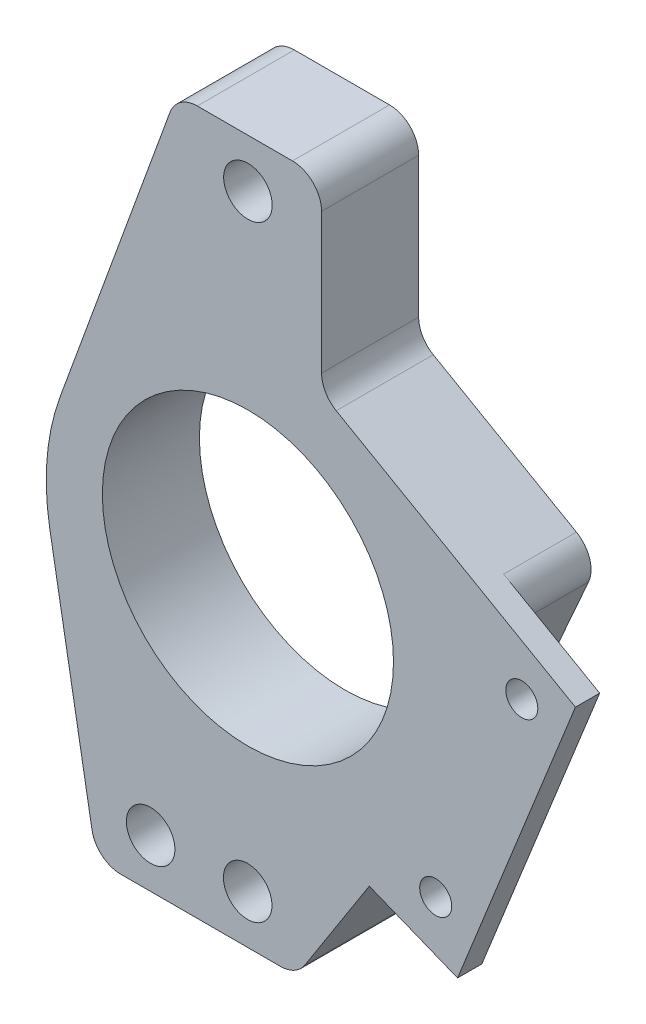
SolidWorks part; units mm, degrees
ref_plane "Front Plane" through (0, 0, 0) normal (0, 0, 1) x (1, 0, 0)
ref_plane "Top Plane" through (0, 0, 0) normal (0, 1, 0) x (1, 0, 0)
ref_plane "Right Plane" through (0, 0, 0) normal (1, 0, 0) x (0, 0, -1)
sketch "Sketch1" plane through (0, 0, 0) normal (0, 0, 1) x (1, 0, 0)
  line L0 (-18.5763, 100.3652) -> (19.2813, 100.3652)
  line L1 (19.2813, 100.3652) -> (19.2813, 51.6625)
  line L2 (19.2813, 51.6625) -> (85.7172, 13.5763)
  line L3 (85.7172, 13.5763) -> (54.8677, -63.2338)
  line L7 (12.6678, -83.786) -> (-39.7037, -83.786)
  line L9 (-39.7037, -83.786) -> (-51.867, -14.6914)
  line L13 (-49.1135, 16.6221) -> (-18.5763, 100.3652)
  line L14 (54.8677, -63.2338) -> (31.7649, -53.955)
  line L15 (31.7649, -53.955) -> (12.6678, -83.786)
  circle A0 centre (0, 0) radius 38.1
  circle A3 centre (0, 87.6652) radius 6.35
  circle A4 centre (-0.0617, -71.086) radius 6.35
  arc A5 (-49.1135, 16.6221) -> (-51.867, -14.6914) centre (7.9035, -4.1694) ccw
  circle A6 centre (-25.4617, -71.0752) radius 6.35
  point P3 (-26.3707, -71.0752)
  point P12 (-52.2832, -11.966)
  dimension "D1" = 76.2
  dimension "D2" = 12.7
  dimension "D3" = 25.4
  dimension "D4" = 12.7
extrude "Boss-Extrude1" add sketch "Sketch1" along normal blind 25.4
sketch "Sketch2" plane through (0, 0, 0) normal (0, 0, 1) x (1, 0, 0)
  line L2 (85.7172, 13.5763) -> (54.8677, -63.2338)
  line L5 (85.7172, 13.5763) -> (66.5382, 24.5712)
  line L6 (85.7172, 13.5763) -> (19.2813, 51.6625) construction
  line L7 (66.5382, 24.5712) -> (31.7649, -53.955)
  line L8 (54.8677, -63.2338) -> (31.7649, -53.955)
extrude "Cut-Extrude1" cut sketch "Sketch2" along normal blind 19.05 contours L8 L7 L5 L2
sketch "Sketch3" plane through (0, 0, 25.4) normal (0, 0, 1) x (1, 0, 0)
  circle A0 centre (71.6792, 8.3618) radius 4.191
  circle A1 centre (49.1489, -47.7348) radius 4.191
  dimension "D1" = 8.382
  dimension "D2" = 8.382
  dimension "D3" = 60.452
extrude "Cut-Extrude2" cut sketch "Sketch3" against normal through all
fillet "Fillet1" radius 7.62 6 edges at (-18.5763, 100.3652, 12.7) (19.2813, 100.3652, 12.7) (19.2813, 51.6625, 12.7) (66.5382, 24.5712, 9.525) (12.6678, -83.786, 12.7) (-39.7037, -83.786, 12.7)
